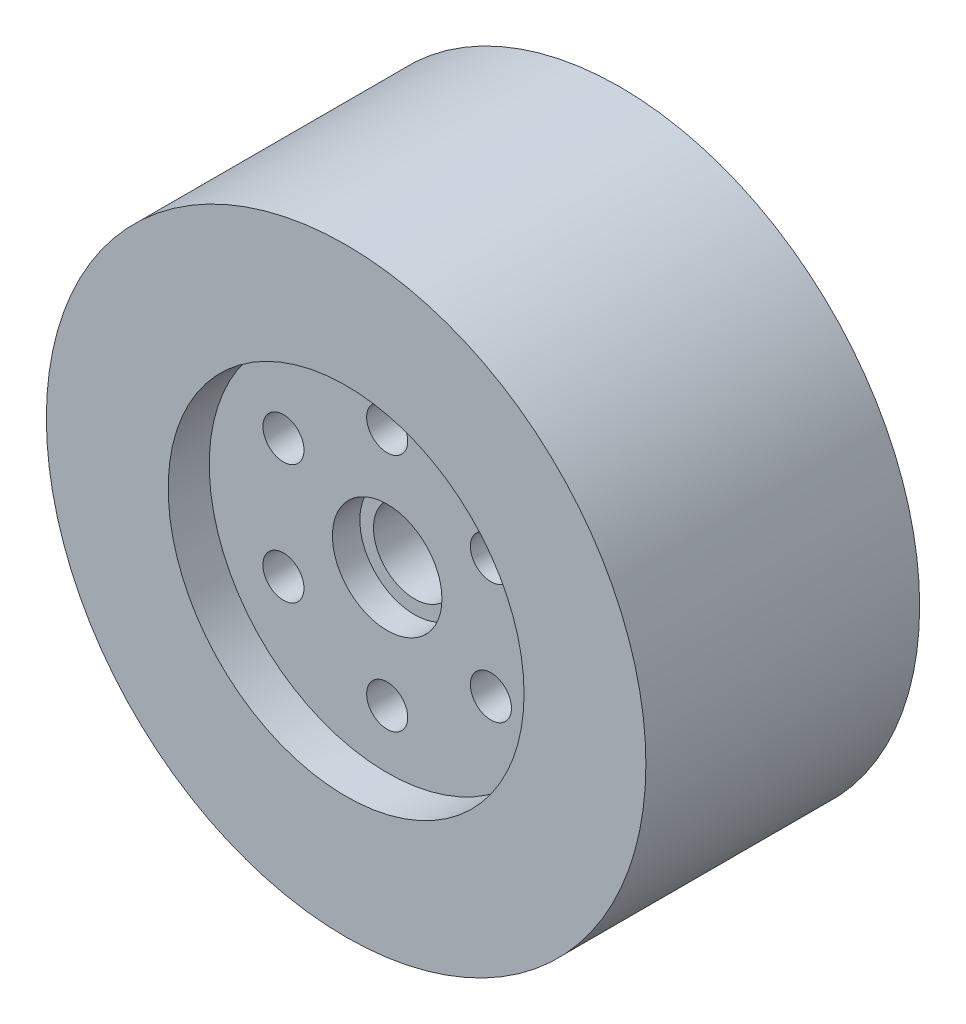
SolidWorks part; units mm, degrees
material "POLYURETHANE (11671)"
ref_plane "Front Plane" through (0, 0, 0) normal (0, 0, 1) x (1, 0, 0)
ref_plane "Top Plane" through (0, 0, 0) normal (0, 1, 0) x (1, 0, 0)
ref_plane "Right Plane" through (0, 0, 0) normal (1, 0, 0) x (0, 0, -1)
sketch "Sketch1" plane through (0, 0, 0) normal (0, 0, 1) x (1, 0, 0)
  circle A0 centre (0, 0) radius 21.9
  dimension "D1" = 43.8
extrude "Boss-Extrude1" add sketch "Sketch1" along normal blind 20
sketch "Sketch2" plane through (0, 0, 20) normal (0, 0, 1) x (1, 0, 0)
  circle A0 centre (0, 0) radius 3
  dimension "D1" = 6
extrude "Cut-Extrude1" cut sketch "Sketch2" against normal through all contours A0
sketch "Sketch4" plane through (0, 0, 0) normal (0, 0, -1) x (-1, 0, 0)
  circle A0 centre (0, 0) radius 4
  dimension "D1" = 8
extrude "Cut-Extrude4" cut sketch "Sketch4" against normal blind 2
sketch "Sketch6" plane through (0, 0, 20) normal (0, 0, 1) x (1, 0, 0)
  circle A0 centre (0, 0) radius 13
  dimension "D1" = 26
extrude "Cut-Extrude6" cut sketch "Sketch6" against normal blind 3
sketch "Sketch9" plane through (0, 0, 17) normal (0, 0, 1) x (1, 0, 0)
  circle A0 centre (0, 8.75) radius 1.5
  dimension "D1" = 3
  dimension "D2" = 8.75
extrude "Cut-Extrude7" cut sketch "Sketch9" against normal blind 5
sketch "Sketch3" plane through (0, 0, 20) normal (0, 0, 1) x (1, 0, 0)
  circle A0 centre (0, 0) radius 4
  dimension "D1" = 8
extrude "Cut-Extrude8" cut sketch "Sketch3" against normal blind 5 contours A0
pattern_circular "CirPattern1" count 6 over 360 about axis through (0, 0, 17) along (0, 0, 1) of "Cut-Extrude7"
